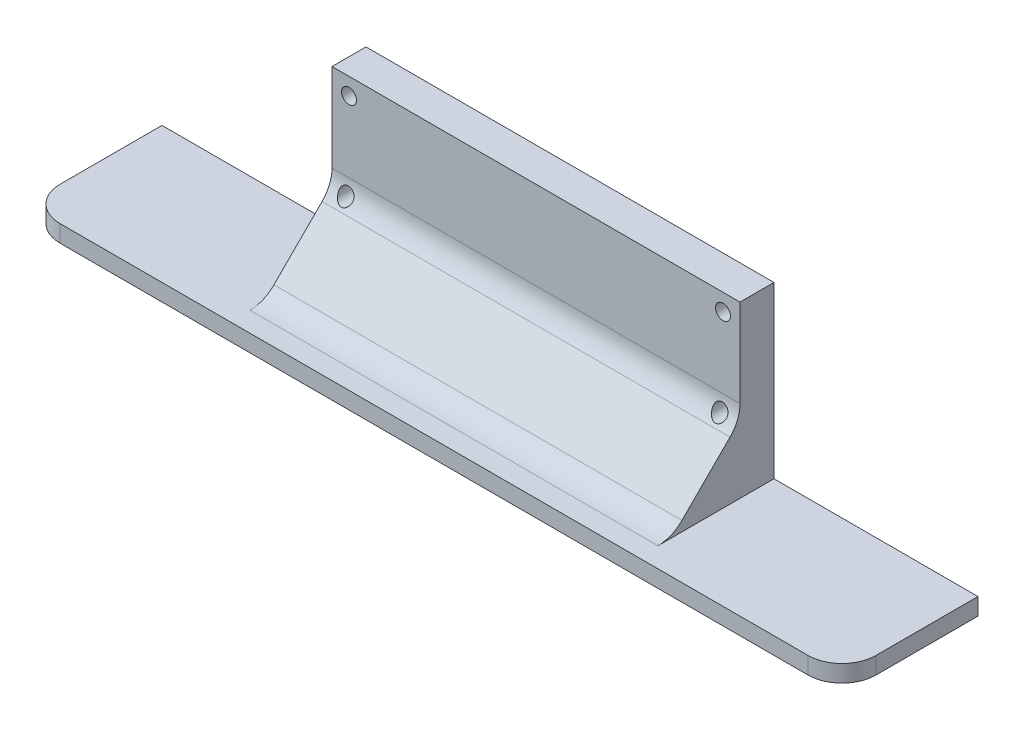
SolidWorks part; units mm, degrees
ref_plane "前视基准面" through (0, 0, 0) normal (0, 0, 1) x (1, 0, 0)
ref_plane "上视基准面" through (0, 0, 0) normal (0, 1, 0) x (1, 0, 0)
ref_plane "右视基准面" through (0, 0, 0) normal (1, 0, 0) x (0, 0, -1)
sketch "草图1" plane through (0, 0, 0) normal (0, 1, 0) x (1, 0, 0)
  line L1 (-120, -20) -> (120, -20)
  line L2 (-120, -20) -> (-120, 20)
  line L3 (-120, 20) -> (120, 20)
  line L4 (120, -20) -> (120, 20)
  line L5 (-120, -20) -> (120, 20) construction
  line L6 (-120, 20) -> (120, -20) construction
  point P0 (0, 0)
  dimension "D1" = 40
  dimension "D2" = 240
extrude "凸台-拉伸1" add sketch "草图1" along normal blind 5
sketch "草图2" plane through (0, 5, 0) normal (0, 1, 0) x (1, 0, 0)
  line L0 (120, 20) -> (-120, 20) construction
  line L1 (-60, 20) -> (60, 20)
  line L2 (-60, 20) -> (-60, 10)
  line L3 (-60, 10) -> (60, 10)
  line L4 (60, 20) -> (60, 10)
  line L5 (-120, 20) -> (-120, -20) construction
  dimension "D1" = 10
  dimension "D2" = 120
  dimension "D3" = 60
extrude "凸台-拉伸2" add sketch "草图2" along normal blind 50
chamfer "倒角1" distance 20 angle 45 1 edges at (0, 5, -10)
fillet "圆角4" radius 10 2 edges at (0, 5, 10) (0, 25, -10)
sketch "草图4" plane through (0, 0, -10) normal (0, 0, 1) x (1, 0, 0)
  line L1 (-55, 50) -> (55, 50) construction
  line L2 (-55, 50) -> (-55, 25) construction
  line L3 (-55, 25) -> (55, 25) construction
  line L4 (55, 50) -> (55, 25) construction
  line L5 (-60, 55) -> (60, 55) construction
  line L6 (-60, 55) -> (-60, 29.1421) construction
  line L7 (60, 55) -> (60, 29.1421) construction
  line L8 (-120, 5) -> (120, 5) construction
  circle A0 centre (-55, 50) radius 2.2
  circle A1 centre (55, 50) radius 2.2
  circle A2 centre (-55, 25) radius 2.2
  circle A3 centre (55, 25) radius 2.2
  dimension "D2" = 4.4
  dimension "D5" = 4.4
  dimension "D6" = 4.4
  dimension "D8" = 4.4
  dimension "D1" = 5
  dimension "D3" = 5
  dimension "D4" = 5
  dimension "D7" = 20
extrude "切除-拉伸1" cut sketch "草图4" against normal through all both and the other way through all
fillet "圆角5" radius 10 2 edges at (-120, 2.5, 20) (120, 2.5, 20)
